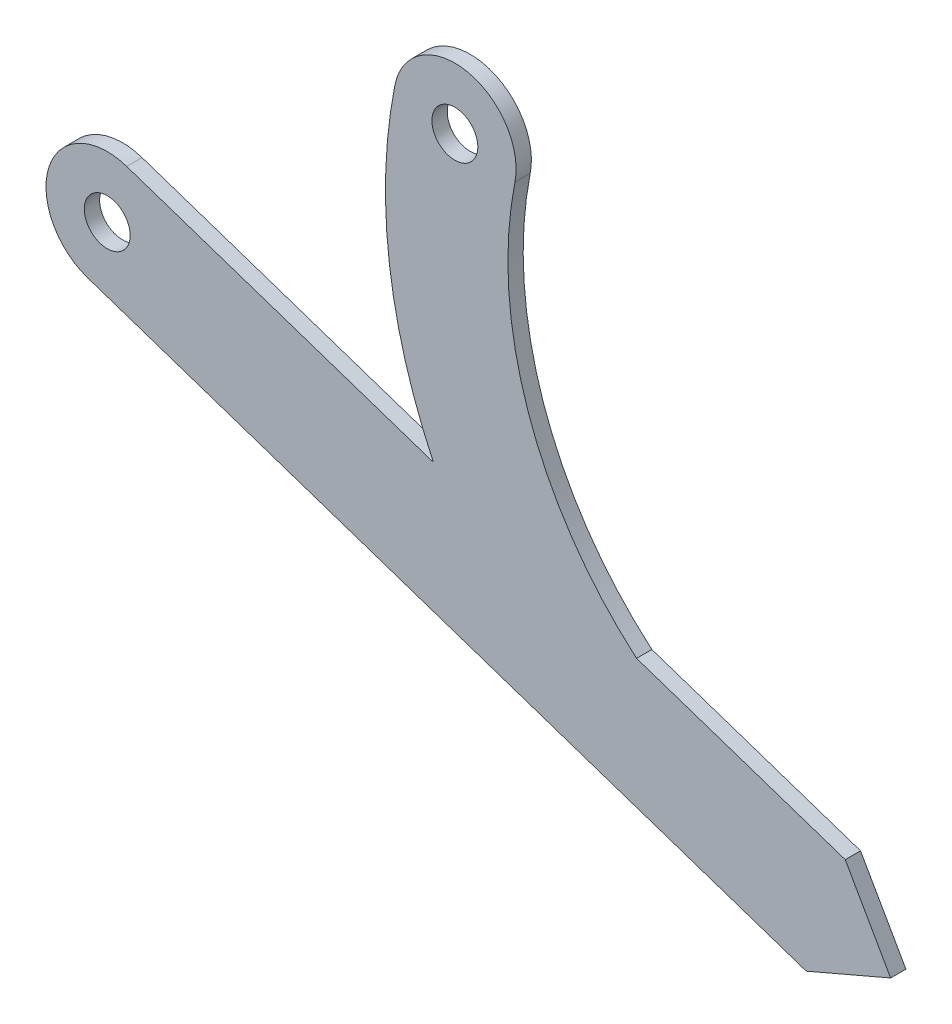
SolidWorks part; units mm, degrees
ref_plane "Front Plane" through (0, 0, 0) normal (0, 0, 1) x (1, 0, 0)
ref_plane "Top Plane" through (0, 0, 0) normal (0, 1, 0) x (1, 0, 0)
ref_plane "Right Plane" through (0, 0, 0) normal (1, 0, 0) x (0, 0, -1)
sketch "Esquisse1" plane through (0, 0, 0) normal (0, 0, 1) x (1, 0, 0)
  line L0 (-54.4671, -50.2361) -> (-3.2717, -67.4127) construction
  line L1 (-53.1947, -46.4439) -> (-33.1491, -53.1694)
  line L2 (-55.7394, -54.0284) -> (-8.7839, -69.7824)
  line L3 (-33.1491, -53.1694) -> (-35.6938, -60.7539) construction
  line L5 (-19.8763, -57.6226) -> (-6.2392, -62.1979)
  line L6 (-3.2717, -67.4127) -> (-8.7839, -69.7824)
  line L7 (-3.2717, -67.4127) -> (-6.2392, -62.1979)
  line L8 (-8.7839, -69.7824) -> (-6.2392, -62.1979) construction
  arc A0 (-31.748, -33.8702) -> (-3.2717, -67.4127) centre (-4.1907, -39.334) ccw construction
  arc A5 (-35.6716, -33.0922) -> (-33.1491, -53.1694) centre (-4.1907, -39.334) ccw
  arc A16 (-27.8244, -34.6481) -> (-19.8763, -57.6226) centre (-4.1907, -39.334) ccw
  arc A17 (-27.8244, -34.6481) -> (-35.6716, -33.0922) centre (-31.748, -33.8702) ccw
  arc A19 (-53.1947, -46.4439) -> (-55.7394, -54.0284) centre (-54.4671, -50.2361) ccw
  circle A21 centre (-54.4671, -50.2361) radius 1.5
  circle A22 centre (-31.748, -33.8702) radius 1.5
  point P3 (-54.0188, -52.6934)
  point P12 (-57.9177, -51.0525)
  dimension "D1" = 6
  dimension "D2" = 8
  dimension "D3" = 3
  dimension "D4" = 8
  dimension "D5" = 14
  dimension "D6" = 8
base flange "Tôle de base pliée1" sketch "Esquisse1" thickness 1 reverse thickness direction yes parameters "D1"=0.7366
sketch "Bend-Lines1" [suppressed] plane through (0, 0, 0) normal (0, 1, 0) x (1, 0, 0)
sketch "Bounding-Box1" [suppressed] plane through (0, 0, 0) normal (0, 1, 0) x (1, 0, 0)
sheet metal parameters "Sheet-Metal1" thickness 1 parameters "D1"=0.7366
flat pattern "Flat-Pattern1" [suppressed]
sketch "Bend-Lines2" plane through (0, 0, 0) normal (0, 0, -1) x (-1, 0, 0)
sketch3d "Bounding-Box2" [suppressed]
  line L0 (26.7312, 11.1345, 0) -> (-1.4549, -27.6896, 0) construction
  line L1 (55.8632, -10.0152, 0) -> (27.6771, -48.8393, 0) construction
  line L2 (26.7312, 11.1345, 0) -> (55.8632, -10.0152, 0) construction
  line L3 (-1.4549, -27.6896, 0) -> (27.6771, -48.8393, 0) construction
